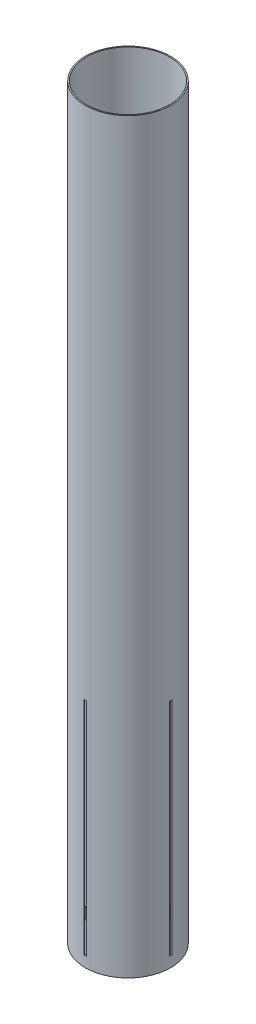
SolidWorks part; units mm, degrees
material "E-Glass Fiber"
ref_plane "Front Plane" through (0, 0, 0) normal (0, 0, 1) x (1, 0, 0)
ref_plane "Top Plane" through (0, 0, 0) normal (0, 1, 0) x (1, 0, 0)
ref_plane "Right Plane" through (0, 0, 0) normal (1, 0, 0) x (0, 0, -1)
sketch "Sustainer Tube Profile" plane through (0, 0, 0) normal (0, 1, 0) x (1, 0, 0)
  circle A0 centre (0, 0) radius 76.2
  circle A1 centre (0, 0) radius 78.359
  dimension "D1" = 152.4
  dimension "D2" = 156.718
extrude "Sustainer Tube Body" add sketch "Sustainer Tube Profile" along normal blind 1371.6
ref_plane "Plane1" through (0, 0, 78.359) normal (0, 0, 1) x (1, 0, 0)
sketch "Fin Slot Profile" plane through (0, 0, 78.359) normal (0, 0, 1) x (1, 0, 0)
  line L0 (0, 0) -> (0, 1371.6) construction
  line L5 (76.2, 1371.6) -> (-76.2, 1371.6) construction
  line L6 (-78.359, 0) -> (78.359, 0) construction
  line L7 (2.3813, 19.05) -> (-2.3813, 19.05)
  line L8 (0, 19.05) -> (0, 425.45)
  line L9 (2.3813, 425.45) -> (-2.3813, 425.45)
  line L10 (-2.3813, 19.05) -> (-2.3813, 425.45)
  line L11 (2.3813, 19.05) -> (2.3813, 425.45)
  dimension "D1" = 406.4
  dimension "D2" = 19.05
  dimension "D3" = 2.3813
extrude "Fin Slot Cut" cut sketch "Fin Slot Profile" against normal up to surface (2.1962 mm away) contours L7 L11 L9 L8 | L10 L7 L8 L9 region at (1.1906, 222.25, 78.359) region at (-1.1906, 222.25, 78.359) up to face at (0, 1371.6, 76.2)
pattern_circular "Fin Slot Pattern" count 4 over 360 about axis through (0, 1371.6, 0) along (0, 1, 0) of "Fin Slot Cut"
equation "\"Length\"= 54"
equation "\"Outer Diameter\"= 6.17"
equation "\"Inner Diameter\"= 6"
equation "\"Wall Thickness\"= 0.085"
equation "\"D1@Sustainer Tube Profile\" = \"Inner Diameter\""
equation "\"D2@Sustainer Tube Profile\" = \"Outer Diameter\""
equation "\"D1@Sustainer Tube Body\" = \"Length\""
equation "\"Root Chord\"= 16"
equation "\"Fin Offset\"= 3 / 4"
equation "\"D1@Fin Slot Profile\"=\"Root Chord\" "
equation "\"D2@Fin Slot Profile\" = \"Fin Offset\""
equation "\"Fin Thickness\"= ( 3 / 16 ) / 2"
equation "\"D3@Fin Slot Profile\"=\"Fin Thickness\""
